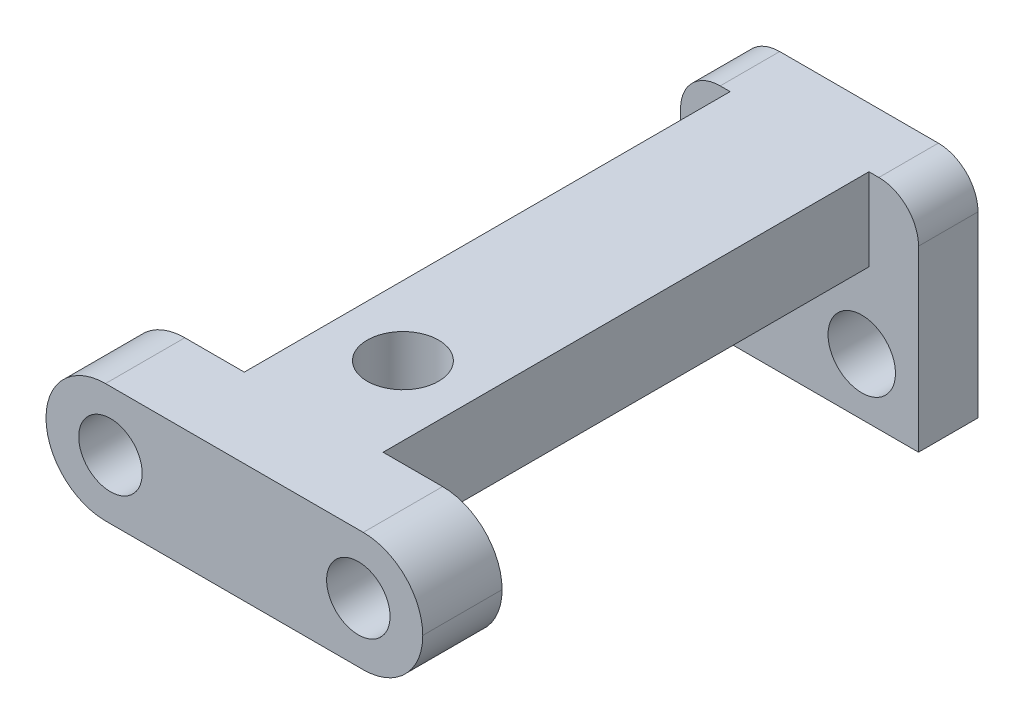
SolidWorks part; units mm, degrees
ref_plane "Front Plane" through (0, 0, 0) normal (0, 0, 1) x (1, 0, 0)
ref_plane "Top Plane" through (0, 0, 0) normal (0, 1, 0) x (1, 0, 0)
ref_plane "Right Plane" through (0, 0, 0) normal (1, 0, 0) x (0, 0, -1)
sketch "Sketch1" plane through (0, 0, 0) normal (0, 0, 1) x (1, 0, 0)
  line L0 (-3.5, 39.8466) -> (-3.5, 44)
  line L1 (-3.5, 44) -> (3.5, 44)
  line L2 (3.5, 44) -> (3.5, 39.8466)
  circle A0 centre (0, 0) radius 40
  dimension "D1" = 80
  dimension "D2" = 44
  dimension "D3" = 7
  dimension "D4" = 3.5
extrude "Boss-Extrude1" add sketch "Sketch1" along normal blind 28.5 contours A0 L2 L1 L0 region at (0, 41.9742, 0)
sketch "Sketch2" plane through (0, 0, 0) normal (0, 0, -1) x (-1, 0, 0)
  line L0 (0, 0) -> (-3.1376, 35.863) construction
  line L1 (-6, 44) -> (6, 44)
  line L2 (-6, 44) -> (-6, 33)
  line L3 (-6, 33) -> (6, 33)
  line L4 (6, 44) -> (6, 33)
  line L5 (-3.5, 44) -> (-3.5, 39.8466) construction
  line L6 (0, 0) -> (0, 45.6591) construction
  line L7 (0, 0) -> (3.1376, 35.863) construction
  circle A0 centre (-3.1376, 35.863) radius 1.7
  circle A1 centre (3.1376, 35.863) radius 1.7
  circle A2 centre (0, 0) radius 36 construction
  point P15 (2.6194, 36.4779)
  point P17 (3.1376, 35.863)
  point P18 (0, 0)
  point P19 (0, 0)
  dimension "D2" = 3.4
  dimension "D3" = 3.4
  dimension "D10" = 72
  dimension "D1" = 11
  dimension "D8" = 12
  dimension "D9" = 2.5
  dimension "D11" = 5
  dimension "D12" = 5
extrude "Boss-Extrude2" add sketch "Sketch2" along normal blind 3
sketch "Sketch3" plane through (0, 0, 28.5) normal (0, 0, 1) x (1, 0, 0)
  line L0 (0, 44) -> (0, 34.329) construction
  line L1 (-3.5, 44) -> (3.5, 44) construction
  line L3 (-9.5, 44) -> (9.5, 44)
  line L4 (-9.5, 44) -> (-9.5, 38)
  line L5 (-9.5, 38) -> (9.5, 38)
  line L6 (9.5, 44) -> (9.5, 38)
  dimension "D1" = 6
  dimension "D2" = 19
extrude "Boss-Extrude3" add sketch "Sketch3" against normal blind 4
hole_wizard "M3 Clearance Hole1" positions "Sketch4" profile "Sketch5" hole size "M3" standard "ANSI Metric" end condition up to next
sketch "Sketch4" plane through (0, 0, 28.5) normal (0, 0, 1) x (1, 0, 0)
  line L0 (-9.5, 44) -> (-9.5, 38) construction
  line L1 (9.5, 38) -> (9.5, 44) construction
  line L2 (-9.5, 44) -> (9.5, 44) construction
  point P0 (-6.25, 41)
  point P2 (6.25, 41)
  dimension "D1" = 3.25
  dimension "D2" = 3.25
  dimension "D3" = 3
  dimension "D4" = 3
sketch "Sketch5" plane through (-6.25, 41, 28.5) normal (1, 0, 0) x (0, -1, 0)
  line L0 (0, 0) -> (0, 4)
  line L1 (0, 4) -> (1.6, 4)
  line L2 (1.6, 4) -> (1.6, 0)
  line L5 (1.6, 0) -> (0, 0)
  line L11 (0, -6.35) -> (0, 107.95) construction
  dimension "Thru Hole Dia." = 3.2
  dimension "Thru Hole Depth" = 4
fillet "Fillet1" radius 3 4 edges at (9.5, 38, 26.5) (9.5, 44, 26.5) (-9.5, 38, 26.5) (-9.5, 44, 26.5)
hole_wizard "M3 Clearance Hole2" positions "Sketch6" profile "Sketch7" hole size "M3" standard "ANSI Metric" end condition through all
sketch "Sketch6" plane through (0, 44, 0) normal (0, 1, 0) x (1, 0, 0)
  line L0 (-6, 3) -> (6, 3) construction
  line L2 (0, -20) -> (3.5, -20) construction
  line L3 (3.5, -24.5) -> (3.5, 0) construction
  line L4 (0, -20) -> (-3.5, -20) construction
  line L5 (-3.5, -24.5) -> (-3.5, 0) construction
  point P0 (0, -20)
  dimension "D1" = 23
sketch "Sketch7" plane through (0, 44, 20) normal (1, 0, 0) x (0, 0, 1)
  line L0 (0, 0) -> (0, 11)
  line L1 (0, 11) -> (1.8, 11)
  line L2 (1.8, 11) -> (1.8, 0)
  line L5 (1.8, 0) -> (0, 0)
  line L11 (0, -6.35) -> (0, 107.95) construction
  dimension "Thru Hole Dia." = 3.6
  dimension "Thru Hole Depth" = 11
fillet "Fillet2" radius 2 2 edges at (-6, 44, -1.5) (6, 44, -1.5)
